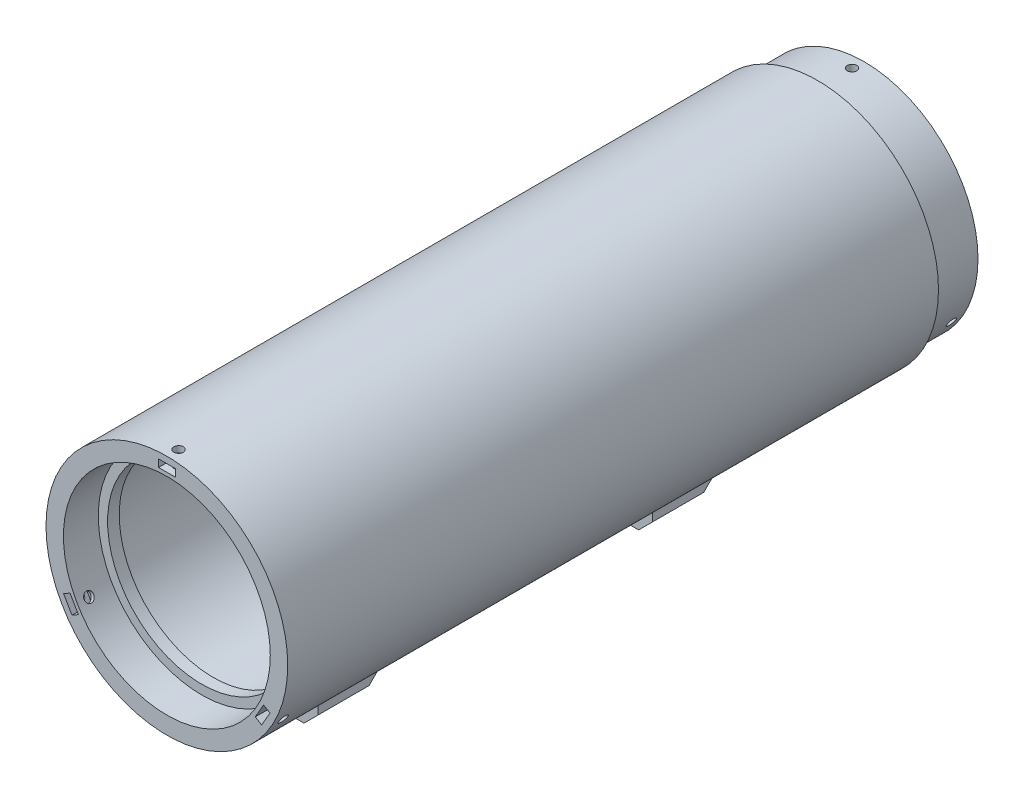
SolidWorks part; units mm, degrees
ref_plane "Front Plane" through (0, 0, 0) normal (0, 0, 1) x (1, 0, 0)
ref_plane "Top Plane" through (0, 0, 0) normal (0, 1, 0) x (1, 0, 0)
ref_plane "Right Plane" through (0, 0, 0) normal (1, 0, 0) x (0, 0, -1)
sketch "Sketch2" plane through (0, 0, 0) normal (0, 0, 1) x (1, 0, 0)
  circle A0 centre (0, 0) radius 23.495
  circle A1 centre (0, 0) radius 31.115
  dimension "D1" = 46.99
  dimension "D2" = 7.62
extrude "Boss-Extrude1" add sketch "Sketch2" along normal blind 12.7
sketch "Sketch3" plane through (0, 0, 12.7) normal (0, 0, 1) x (1, 0, 0)
  circle A0 centre (0, 0) radius 23.495
  circle A1 centre (0, 0) radius 19.685
  circle A2 centre (0, 0) radius 23.495 construction
  dimension "D1" = 3.81
  dimension "D2" = 0
extrude "Boss-Extrude2" add sketch "Sketch3" against normal blind 6.35
ref_plane "Plane1" through (0, 31.115, 0) normal (0, 1, 0) x (1, 0, 0)
hole_wizard "M2 Clearance Hole1" positions "Sketch6" profile "Sketch5" hole size "M2" standard "ANSI Metric" end condition up to next
sketch "Sketch6" plane through (0, 31.115, 0) normal (0, 1, 0) x (1, 0, 0)
  line L1 (31.115, 0) -> (-31.115, 0) construction
  point P0 (-0.127, -3.175)
  dimension "D1" = 3.175
sketch "Sketch5" plane through (-0.127, 31.115, 3.175) normal (1, 0, 0) x (0, 0, 1)
  line L0 (0, 0) -> (0, 62.2297)
  line L1 (0, 62.2297) -> (1.3, 62.2297)
  line L2 (1.3, 62.2297) -> (1.3, 0)
  line L5 (1.3, 0) -> (0, 0)
  line L11 (0, -6.35) -> (0, 107.95) construction
  dimension "Thru Hole Dia." = 2.6
  dimension "Thru Hole Depth" = 62.2297
pattern_circular "CirPattern1" count 3 over 360 about axis through (0, 0, 0) along (0, 0, 1) of "M2 Clearance Hole1"
sketch "Sketch7" plane through (0, 0, 0) normal (0, 0, -1) x (-1, 0, 0)
  line L0 (-1.173, 31.0929) -> (-1.173, 23.4657) construction
  line L1 (-2.189, 27.305) -> (2.383, 27.305)
  line L2 (-2.189, 27.305) -> (-2.189, 25.4)
  line L3 (-2.189, 25.4) -> (2.383, 25.4)
  line L4 (2.383, 27.305) -> (2.383, 25.4)
  line L6 (-1.173, 31.0929) -> (-1.173, 23.4657) construction
  circle A0 centre (0, 0) radius 23.495 construction
  dimension "D1" = 1.905
  dimension "D2" = 4.572
  dimension "D3" = 25.4
  dimension "D4" = 1.016
  dimension "D5" = 3.556
extrude "Cut-Extrude1" cut sketch "Sketch7" against normal blind 5.461
pattern_circular "CirPattern2" count 3 over 360 about axis through (0, 0, 0) along (0, 0, 1) of "Cut-Extrude1"
sketch "Sketch8" plane through (0, 0, 12.7) normal (0, 0, 1) x (1, 0, 0)
  circle A0 centre (0, 0) radius 33.02
  circle A1 centre (0, 0) radius 28.2575
  dimension "D1" = 66.04
  dimension "D2" = 56.515
extrude "Boss-Extrude3" add sketch "Sketch8" along normal blind 177.8
ref_plane "Plane3" through (0, 33.02, 0) normal (0, 1, 0) x (1, 0, 0)
hole_wizard "M2 Clearance Hole2" positions "Sketch10" profile "Sketch9" hole size "M2" standard "ANSI Metric" end condition up to next
sketch "Sketch10" plane through (0, 33.02, 0) normal (0, 1, 0) x (1, 0, 0)
  line L0 (-33.02, -190.5) -> (33.02, -190.5) construction
  line L1 (-33.02, -12.7) -> (-33.02, -190.5) construction
  point P0 (0, -187.325)
  dimension "D1" = 3.175
  dimension "D2" = 33.02
sketch "Sketch9" plane through (0, 33.02, 187.325) normal (1, 0, 0) x (0, 0, 1)
  line L0 (0, 0) -> (0, 66.04)
  line L1 (0, 66.04) -> (1.3, 66.04)
  line L2 (1.3, 66.04) -> (1.3, 0)
  line L5 (1.3, 0) -> (0, 0)
  line L11 (0, -6.35) -> (0, 107.95) construction
  dimension "Thru Hole Dia." = 2.6
  dimension "Thru Hole Depth" = 66.04
sketch "Sketch11" plane through (0, 0, 190.5) normal (0, 0, 1) x (1, 0, 0)
  line L1 (-2.256, 31.242) -> (2.316, 31.242)
  line L2 (-2.256, 31.242) -> (-2.256, 29.21)
  line L3 (-2.256, 29.21) -> (2.316, 29.21)
  line L4 (2.316, 31.242) -> (2.316, 29.21)
  line L6 (-1.3, 32.9944) -> (-1.3, 28.2276) construction
  line L7 (1.3, 28.2276) -> (1.3, 32.9944) construction
  circle A0 centre (0, 0) radius 33.02 construction
  dimension "D1" = 4.572
  dimension "D2" = 2.032
  dimension "D3" = 0.956
  dimension "D4" = 1.016
  dimension "D5" = 31.242
extrude "Cut-Extrude2" cut sketch "Sketch11" against normal blind 5.461
ref_plane "Plane4" through (0, 0, 184.15) normal (0, 0, 1) x (1, 0, 0)
sketch "Sketch12" plane through (0, 0, 184.15) normal (0, 0, 1) x (1, 0, 0)
  circle A0 centre (0, 0) radius 28.2575
  circle A1 centre (0, 0) radius 25.7175
  circle A2 centre (0, 0) radius 28.2575 construction
  dimension "D1" = 0
  dimension "D2" = 2.54
extrude "Boss-Extrude4" add sketch "Sketch12" against normal blind 6.35
pattern_circular "CirPattern3" count 3 over 360 about axis through (0, 0, 190.5) along (0, 0, 1) of "M2 Clearance Hole2", "Cut-Extrude2"
sketch "Sketch13" plane through (0, 0, 0) normal (0, 0, -1) x (-1, 0, 0)
  circle A0 centre (0, 0) radius 34.445
extrude "Cut-Extrude4" [suppressed] cut sketch "Sketch13" against normal blind 177.8
sketch "Sketch14" plane through (0, 0, 184.15) normal (0, 0, 1) x (1, 0, 0)
  circle A0 centre (0, 0) radius 28.2575
  circle A1 centre (0, 0) radius 25.7175
  circle A2 centre (0, 0) radius 25.7175 construction
  circle A3 centre (0, 0) radius 28.2575 construction
  dimension "D1" = 0
  dimension "D2" = 0
extrude "Cut-Extrude5" cut sketch "Sketch14" against normal blind 3.175
ref_plane "Plane5" through (0, -30.48, 0) normal (0, 1, 0) x (1, 0, 0)
sketch "Sketch15" plane through (0, -30.48, 0) normal (0, 1, 0) x (1, 0, 0)
  line L0 (0, -36.322) -> (0, 36.322) construction
  line L1 (-9.525, -158.75) -> (9.525, -158.75)
  line L2 (-9.525, -158.75) -> (-9.525, -135.89)
  line L3 (-9.525, -135.89) -> (9.525, -135.89)
  line L4 (9.525, -158.75) -> (9.525, -135.89)
  line L5 (-9.525, -67.31) -> (9.525, -67.31)
  line L6 (-9.525, -67.31) -> (-9.525, -44.45)
  line L7 (-9.525, -44.45) -> (9.525, -44.45)
  line L8 (9.525, -67.31) -> (9.525, -44.45)
  line L9 (-28.2575, -190.5) -> (28.2575, -190.5) construction
  line L10 (31.115, -12.7) -> (-31.115, -12.7) construction
  dimension "D1" = 19.05
  dimension "D2" = 19.05
  dimension "D3" = 22.86
  dimension "D4" = 22.86
  dimension "D5" = 9.525
  dimension "D6" = 9.525
  dimension "D7" = 31.75
  dimension "D8" = 31.75
extrude "Boss-Extrude5" add sketch "Sketch15" against normal blind 12.7
hole_wizard "1/4 Clearance Hole1" positions "Sketch17" profile "Sketch16" hole size "1/4" standard "ANSI Inch"
sketch "Sketch17" plane through (0, -43.18, 0) normal (0, -1, 0) x (-1, 0, 0)
  line L0 (-9.525, -158.75) -> (9.525, -158.75) construction
  line L1 (-9.525, -158.75) -> (-9.525, -135.89) construction
  line L4 (-9.525, -67.31) -> (-9.525, -44.45) construction
  line L5 (9.525, -67.31) -> (-9.525, -67.31) construction
  point P0 (0, -153.67)
  point P2 (0, -62.23)
  dimension "D1" = 5.08
  dimension "D2" = 9.525
  dimension "D3" = 5.08
  dimension "D4" = 9.525
sketch "Sketch16" plane through (0, -43.18, 153.67) normal (1, 0, 0) x (0, 0, -1)
  line L0 (0, 0) -> (0, 12.7)
  line L1 (0, 12.7) -> (3.5712, 12.7)
  line L2 (3.5712, 12.7) -> (3.5712, 0)
  line L5 (3.5712, 0) -> (0, 0)
  line L10 (0, 12.7) -> (-3.5712, 12.7) construction
  line L11 (0, -6.35) -> (0, 107.95) construction
  dimension "Hole Dia." = 7.1425
  dimension "Hole Depth" = 12.7
  dimension "Drill Angle" = 180
sketch "Sketch18" plane through (0, 0, 158.75) normal (0, 0, 1) x (1, 0, 0)
  line L0 (9.525, -43.18) -> (9.525, -31.6164) construction
  line L1 (-5.715, -34.417) -> (5.715, -34.417)
  line L2 (-5.715, -34.417) -> (-5.715, -40.259)
  line L3 (-5.715, -40.259) -> (5.715, -40.259)
  line L4 (5.715, -34.417) -> (5.715, -40.259)
  line L5 (-9.525, -43.18) -> (9.525, -43.18) construction
  dimension "D1" = 5.842
  dimension "D2" = 11.43
  dimension "D3" = 3.81
  dimension "D4" = 2.921
extrude "Cut-Extrude6" cut sketch "Sketch18" against normal blind 11.43
chamfer "Chamfer2" distance 3.81 angle 45 4 edges at (9.525, -43.18, 55.88) (-9.525, -43.18, 55.88) (9.525, -43.18, 147.32) (-9.525, -43.18, 147.32)
chamfer "Chamfer3" distance 12.7 angle 45 2 edges at (0, -43.18, 135.89) (0, -43.18, 44.45)
sketch "Sketch19" plane through (0, 0, 67.31) normal (0, 0, 1) x (1, 0, 0)
  line L1 (-5.715, -34.417) -> (5.715, -34.417)
  line L2 (-5.715, -34.417) -> (-5.715, -40.259)
  line L3 (-5.715, -40.259) -> (5.715, -40.259)
  line L4 (5.715, -34.417) -> (5.715, -40.259)
extrude "Cut-Extrude7" cut sketch "Sketch19" against normal blind 11.43
equation "\"D1@Cut-Extrude1\"=0.1/2+.04+.125"
equation "\"D1@Cut-Extrude2\"=0.1/2+.04+.125"
equation "\"D5@Sketch15\"=\"D1@Sketch15\"/2"
equation "\"D2@Sketch15\"=\"D1@Sketch15\""
equation "\"D3@Sketch15\"=\"D4@Sketch15\""
equation "\"D6@Sketch15\"=\"D2@Sketch15\"/2"
equation "\"D4@Sketch17\"=\"D2@Sketch17\""
equation "\"D3@Sketch17\"=\"D1@Sketch17\""
equation "\"D2@Sketch17\"=.75/2"
equation "\"D3@Sketch18\"=(.75-\"D2@Sketch18\")/2"
equation "\"D4@Sketch18\"=(.46-\"D1@Sketch18\")/2"
